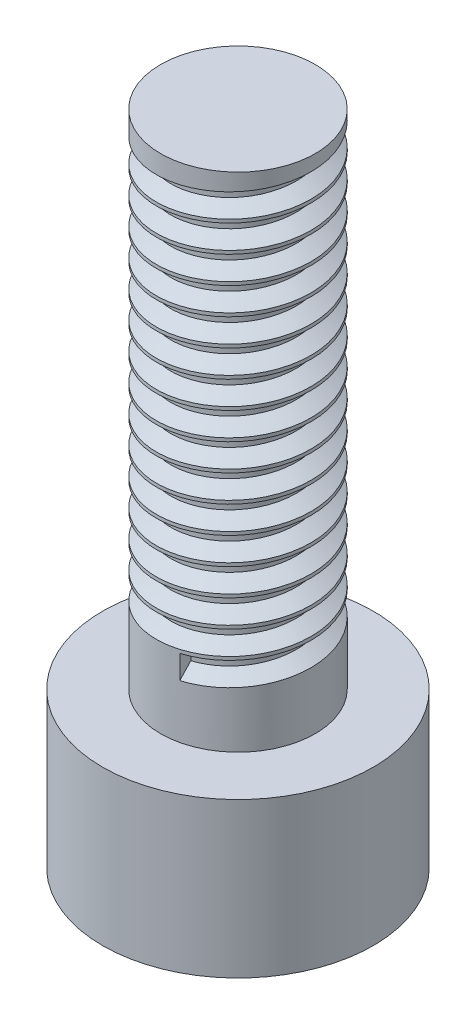
SolidWorks part; units mm, degrees
ref_plane "Front Plane" through (0, 0, 0) normal (0, 0, 1) x (1, 0, 0)
ref_plane "Top Plane" through (0, 0, 0) normal (0, 1, 0) x (1, 0, 0)
ref_plane "Right Plane" through (0, 0, 0) normal (1, 0, 0) x (0, 0, -1)
sketch "Sketch1" plane through (0, 0, 0) normal (0, 1, 0) x (1, 0, 0)
  circle A0 centre (0, 0) radius 3.5
  dimension "D1" = 7
extrude "Boss-Extrude1" add sketch "Sketch1" along normal blind 4
sketch "Sketch2" plane through (0, 4, 0) normal (0, 1, 0) x (1, 0, 0)
  circle A0 centre (0, 0) radius 2
extrude "Boss-Extrude2" add sketch "Sketch2" along normal blind 13
sketch "Sketch3" plane through (0, 0, 0) normal (0, -1, 0) x (1, 0, 0)
  line L1 (1.1678, -1.9924) -> (2.3094, 0.0152)
  line L2 (2.3094, 0.0152) -> (1.1415, 2.0076)
  line L3 (1.1415, 2.0076) -> (-1.1678, 1.9924)
  line L4 (-1.1678, 1.9924) -> (-2.3094, -0.0152)
  line L5 (-2.3094, -0.0152) -> (-1.1415, -2.0076)
  line L6 (-1.1415, -2.0076) -> (1.1678, -1.9924)
  circle A0 centre (0, 0) radius 2 construction
  dimension "D1" = 4
extrude "Cut-Extrude1" cut sketch "Sketch3" against normal blind 2.5
thread "Thread1" pitch 0.7 method cut profile "Thread Profile1" start angle 0, offset 0, length 11, pitch 0.7, diameter 4
ref_plane "Plane1" through (-2, 17, 0) normal (0, 0, 1) x (-1, 0, 0)
sketch "Thread Profile1" plane through (-2, 17, 0) normal (0, 0, 1) x (-1, 0, 0)
  line L0 (0, 0) -> (0, 0.7) construction
  line L11 (0, 0) -> (0, 0.6125)
  line L12 (0, 0.6125) -> (-0.3789, 0.3937)
  line L13 (-0.3789, 0.3937) -> (-0.3789, 0.2187)
  line L15 (-0.3789, 0.2187) -> (0, 0)
  line L17 (-0.3789, 0.3062) -> (0, 0.3062) construction
  point P2 (0, 0)
  dimension "Pitch" = 0.7
  dimension "Profile_Angle" = 60
  dimension "Profile_Land" = 0.175
  dimension "Profile_Height" = 0.3789
